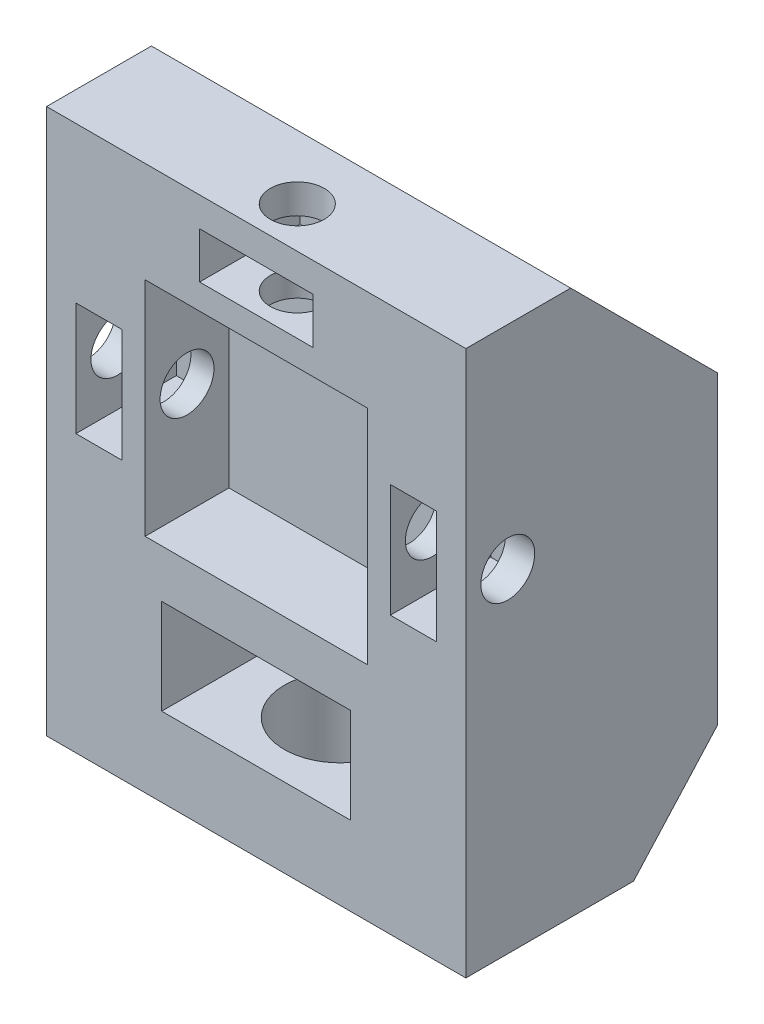
SolidWorks part; units mm, degrees
ref_plane "Front Plane" through (0, 0, 0) normal (0, 0, 1) x (1, 0, 0)
ref_plane "Top Plane" through (0, 0, 0) normal (0, 1, 0) x (1, 0, 0)
ref_plane "Right Plane" through (0, 0, 0) normal (1, 0, 0) x (0, 0, -1)
sketch "Sketch1" plane through (0, 0, 0) normal (0, 0, 1) x (1, 0, 0)
  line L0 (-12.7, -16.51) -> (12.7, -16.51)
  line L1 (-12.7, -16.51) -> (-12.7, 16.51)
  line L2 (12.7, -16.51) -> (12.7, 16.51)
  line L3 (-12.7, 16.51) -> (12.7, 16.51)
  line L4 (-12.7, -16.51) -> (12.7, 16.51) construction
  line L5 (12.7, -16.51) -> (-12.7, 16.51) construction
  point P1 (0, 0)
  dimension "D1" = 25.4
  dimension "D2" = 33.02
extrude "Boss-Extrude1" add sketch "Sketch1" along normal blind 15.24
sketch "Sketch2" plane through (0, 0, 15.24) normal (0, 0, 1) x (1, 0, 0)
  line L1 (-6.731, -3.0541) -> (6.731, -3.0541)
  line L2 (-6.731, -3.0541) -> (-6.731, 10.4079)
  line L3 (-6.731, 10.4079) -> (6.731, 10.4079)
  line L4 (6.731, -3.0541) -> (6.731, 10.4079)
  line L5 (-6.731, -3.0541) -> (6.731, 10.4079) construction
  line L6 (-6.731, 10.4079) -> (6.731, -3.0541) construction
  line L7 (12.7, -16.51) -> (12.7, 16.51) construction
  line L8 (-12.7, 16.51) -> (-12.7, -16.51) construction
  dimension "D1" = 13.462
  dimension "D2" = 13.462
  dimension "D3" = 5.969
  dimension "D4" = 5.969
extrude "Cut-Extrude1" cut sketch "Sketch2" against normal blind 5.08
sketch "Sketch3" plane through (0, 0, 15.24) normal (0, 0, 1) x (1, 0, 0)
  line L1 (-5.7265, -5.9628) -> (5.7265, -5.9628)
  line L2 (-5.7265, -5.9628) -> (-5.7265, -11.7253)
  line L3 (-5.7265, -11.7253) -> (5.7265, -11.7253)
  line L4 (5.7265, -5.9628) -> (5.7265, -11.7253)
  line L5 (-5.7265, -5.9628) -> (5.7265, -11.7253) construction
  line L6 (-5.7265, -11.7253) -> (5.7265, -5.9628) construction
  point P0 (0, -8.8441)
extrude "Cut-Extrude2" cut sketch "Sketch3" against normal through all
chamfer "Chamfer1" distance 5.08 angle 48 1 edges at (0, -16.51, 0) first distance on face at (0, -16.51, 7.62)
hole_wizard "1/4 Clearance Hole1" positions "Sketch5" profile "Sketch6" hole size "1/4" standard "ANSI Inch" end condition up to next
sketch "Sketch5" plane through (0, -16.51, 0) normal (0, -1, 0) x (-1, 0, 0)
  line L0 (12.7, -15.24) -> (-12.7, -15.24) construction
  point P0 (0, -10.16)
  point P3 (0, -10.16)
  dimension "D1" = 5.08
sketch "Sketch6" plane through (0, -16.51, 10.16) normal (1, 0, 0) x (0, 0, -1)
  line L0 (0, 0) -> (0, 13.4559)
  line L1 (0, 13.4559) -> (3.3782, 13.4559)
  line L2 (3.3782, 13.4559) -> (3.3782, 0)
  line L5 (3.3782, 0) -> (0, 0)
  line L11 (0, -6.35) -> (0, 107.95) construction
  dimension "Thru Hole Dia." = 6.7564
  dimension "Thru Hole Depth" = 13.4559
hole_wizard "#4 Clearance Hole1" positions "Sketch8" profile "Sketch7" hole size "#4" standard "ANSI Inch" end condition up to next
sketch "Sketch8" plane through (0, 16.51, 0) normal (0, 1, 0) x (1, 0, 0)
  point P0 (0, -12.7523)
sketch "Sketch7" plane through (0, 16.51, 12.7523) normal (1, 0, 0) x (0, 0, 1)
  line L0 (0, 0) -> (0, 6.1021)
  line L1 (0, 6.1021) -> (1.6319, 6.1021)
  line L2 (1.6319, 6.1021) -> (1.6319, 0)
  line L5 (1.6319, 0) -> (0, 0)
  line L11 (0, -6.35) -> (0, 107.95) construction
  dimension "Thru Hole Dia." = 3.2639
  dimension "Thru Hole Depth" = 6.1021
hole_wizard "#4 Clearance Hole2" positions "Sketch10" profile "Sketch9" hole size "#4" standard "ANSI Inch" end condition through all
sketch "Sketch10" plane through (12.7, 0, 0) normal (1, 0, 0) x (0, 0, -1)
  line L0 (-10.16, -3.0541) -> (-15.24, -3.0541) construction
  line L1 (-10.16, 10.4079) -> (-15.24, 10.4079) construction
  point P0 (-12.7, 3.6769)
  dimension "D1" = 6.731
  dimension "D2" = 6.731
sketch "Sketch9" plane through (12.7, 3.6769, 12.7) normal (0, 1, 0) x (0, 0, -1)
  line L0 (0, 0) -> (0, 25.4)
  line L1 (0, 25.4) -> (1.6319, 25.4)
  line L2 (1.6319, 25.4) -> (1.6319, 0)
  line L5 (1.6319, 0) -> (0, 0)
  line L11 (0, -6.35) -> (0, 107.95) construction
  dimension "Thru Hole Dia." = 3.2639
  dimension "Thru Hole Depth" = 25.4
chamfer "Chamfer2" distance 8.89 angle 45 1 edges at (0, 16.51, 0)
sketch "Sketch11" plane through (0, 0, 15.24) normal (0, 0, 1) x (1, 0, 0)
  line L1 (-3.429, 11.938) -> (3.429, 11.938)
  line L2 (-3.429, 11.938) -> (-3.429, 14.732)
  line L3 (-3.429, 14.732) -> (3.429, 14.732)
  line L4 (3.429, 11.938) -> (3.429, 14.732)
  line L5 (-3.429, 11.938) -> (3.429, 14.732) construction
  line L6 (-3.429, 14.732) -> (3.429, 11.938) construction
  line L7 (8.128, 0.2381) -> (10.922, 0.2381)
  line L8 (8.128, 0.2381) -> (8.128, 7.0961)
  line L9 (8.128, 7.0961) -> (10.922, 7.0961)
  line L10 (10.922, 0.2381) -> (10.922, 7.0961)
  line L11 (8.128, 0.2381) -> (10.922, 7.0961) construction
  line L12 (8.128, 7.0961) -> (10.922, 0.2381) construction
  line L13 (-10.922, 0.2381) -> (-8.128, 0.2381)
  line L14 (-10.922, 0.2381) -> (-10.922, 7.0961)
  line L15 (-10.922, 7.0961) -> (-8.128, 7.0961)
  line L16 (-8.128, 0.2381) -> (-8.128, 7.0961)
  line L17 (-10.922, 0.2381) -> (-8.128, 7.0961) construction
  line L18 (-10.922, 7.0961) -> (-8.128, 0.2381) construction
  line L21 (12.7, -16.51) -> (12.7, 16.51) construction
  line L22 (6.731, -3.0541) -> (6.731, 10.4079) construction
  line L23 (-12.7, 16.51) -> (-12.7, -16.51) construction
  line L24 (-6.731, 10.4079) -> (-6.731, -3.0541) construction
  line L27 (12.7, 16.51) -> (-12.7, 16.51) construction
  point P0 (0, 13.335)
  point P5 (9.525, 3.6671)
  point P10 (-9.525, 3.6671)
  dimension "D1" = 1.778
  dimension "D2" = 2.794
  dimension "D3" = 1.778
  dimension "D4" = 1.397
  dimension "D5" = 2.794
  dimension "D6" = 1.778
  dimension "D7" = 1.397
  dimension "D8" = 2.794
  dimension "D9" = 1.5301
  dimension "D10" = 6.858
  dimension "D11" = 6.858
  dimension "D12" = 6.858
extrude "Cut-Extrude3" cut sketch "Sketch11" against normal blind 6.0833
